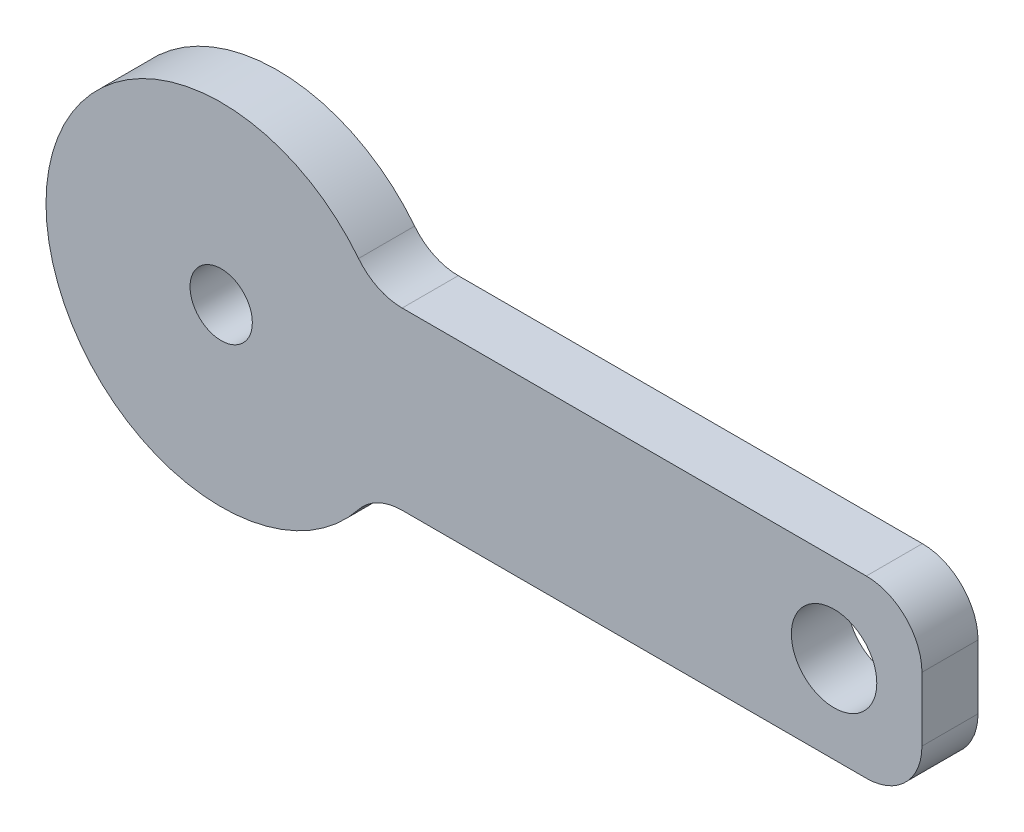
SolidWorks part; units mm, degrees
material "6061-T4 (SS)"
ref_plane "Front Plane" through (0, 0, 0) normal (0, 0, 1) x (1, 0, 0)
ref_plane "Top Plane" through (0, 0, 0) normal (0, 1, 0) x (1, 0, 0)
ref_plane "Right Plane" through (0, 0, 0) normal (1, 0, 0) x (0, 0, -1)
sketch "Sketch1" plane through (0, 0, 0) normal (0, 0, 1) x (1, 0, 0)
  line L1 (5.166, -2.5) -> (18.4125, -2.5)
  line L3 (5.166, 2.5) -> (18.4125, 2.5)
  line L4 (20, -0.9125) -> (20, 0.9125)
  arc A0 (3.9211, 3.1025) -> (3.9211, -3.1025) centre (0, 0) ccw
  arc A1 (5.166, -2.5) -> (3.9211, -3.1025) centre (5.166, -4.0875) ccw
  arc A2 (5.166, 2.5) -> (3.9211, 3.1025) centre (5.166, 4.0875) cw
  arc A3 (18.4125, 2.5) -> (20, 0.9125) centre (18.4125, 0.9125) cw
  arc A4 (18.4125, -2.5) -> (20, -0.9125) centre (18.4125, -0.9125) ccw
  point P12 (20, 2.5)
  point P15 (20, -2.5)
  dimension "D2" = 10
  dimension "D4" = 1.5875
  dimension "D5" = 1.5875
  dimension "D1" = 20
  dimension "D3" = 5
extrude "Boss-Extrude1" add sketch "Sketch1" along normal blind 1.6002
hole_wizard "#0 Clearance Hole1" positions "Sketch2" profile "Sketch3" hole size "#0" standard "ANSI Inch" end condition through all
sketch "Sketch2" plane through (0, 0, 1.6002) normal (0, 0, 1) x (1, 0, 0)
  point P0 (0, 0)
sketch "Sketch3" plane through (0, 0, 1.6002) normal (1, 0, 0) x (0, -1, 0)
  line L0 (0, 0) -> (0, 1.6002)
  line L1 (0, 1.6002) -> (0.889, 1.6002)
  line L2 (0.889, 1.6002) -> (0.889, 0)
  line L5 (0.889, 0) -> (0, 0)
  line L11 (0, -6.35) -> (0, 107.95) construction
  dimension "Thru Hole Dia." = 1.778
  dimension "Thru Hole Depth" = 1.6002
hole_wizard "#2 Clearance Hole1" positions "Sketch4" profile "Sketch5" hole size "#2" standard "ANSI Inch" end condition through all
sketch "Sketch4" plane through (0, 0, 1.6002) normal (0, 0, 1) x (1, 0, 0)
  line L5 (17.4926, 2.5) -> (17.4926, -2.5) construction
  line L6 (18.4125, 2.5) -> (5.166, 2.5) construction
  line L7 (5.166, -2.5) -> (18.4125, -2.5) construction
  circle A6 centre (17.4926, 0) radius 0.889 construction
  point P0 (17.4926, 0)
  point P38 (0, 0)
  point P39 (16.1044, 0)
  point P42 (15.5782, 0)
sketch "Sketch5" plane through (17.4926, 0, 1.6002) normal (1, 0, 0) x (0, -1, 0)
  line L0 (0, 0) -> (0, 1.6002)
  line L1 (0, 1.6002) -> (1.2192, 1.6002)
  line L2 (1.2192, 1.6002) -> (1.2192, 0)
  line L5 (1.2192, 0) -> (0, 0)
  line L11 (0, -6.35) -> (0, 107.95) construction
  dimension "Thru Hole Dia." = 2.4384
  dimension "Thru Hole Depth" = 1.6002
